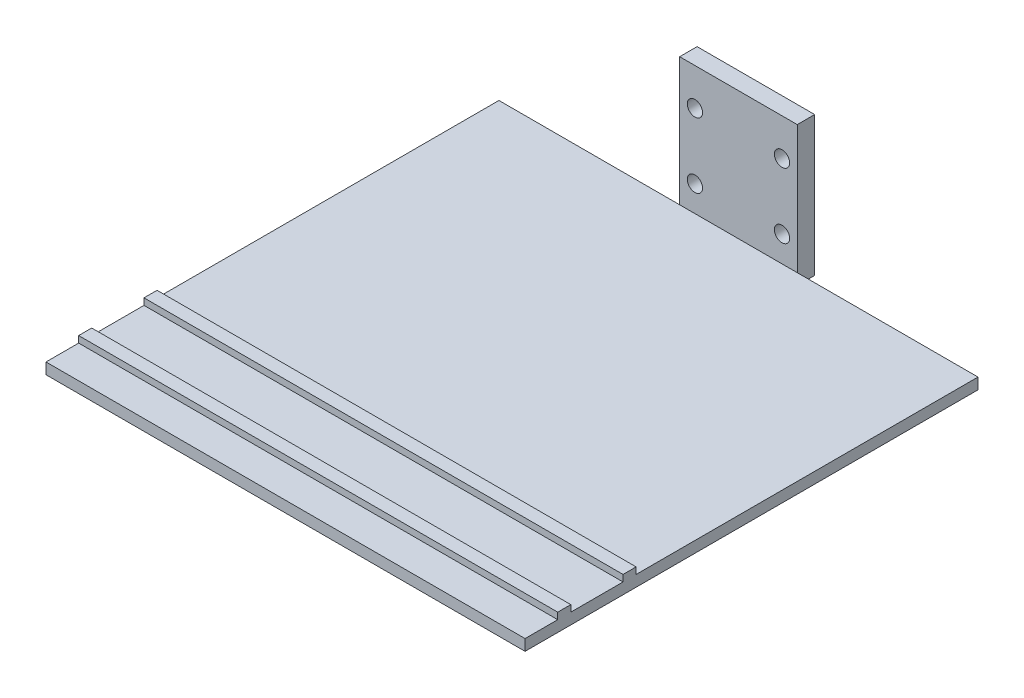
SolidWorks part; units mm, degrees
ref_plane "Piano frontale" through (0, 0, 0) normal (0, 0, 1) x (1, 0, 0)
ref_plane "Piano superiore" through (0, 0, 0) normal (0, 1, 0) x (1, 0, 0)
ref_plane "Piano destro" through (0, 0, 0) normal (1, 0, 0) x (0, 0, -1)
sketch "Schizzo1" plane through (0, 0, 0) normal (0, 0, 1) x (1, 0, 0)
  line L1 (0, 0) -> (27, 0)
  line L2 (0, 0) -> (0, -36)
  line L3 (0, -36) -> (27, -36)
  line L4 (27, 0) -> (27, -36)
  dimension "D1" = 27
  dimension "D2" = 36
extrude "Estrusione-Estrusione1" add sketch "Schizzo1" along normal blind 4
sketch "Schizzo10" plane through (0, 0, 4) normal (0, 0, 1) x (1, 0, 0)
  line L0 (27, 0) -> (0, 0) construction
  line L1 (3.5, -12.5) -> (23.5, -12.5) construction
  line L2 (3.5, -12.5) -> (3.5, -27.5) construction
  line L3 (3.5, -27.5) -> (23.5, -27.5) construction
  line L4 (23.5, -12.5) -> (23.5, -27.5) construction
  line L5 (27, -36) -> (27, 0) construction
  circle A0 centre (3.5, -12.5) radius 1.75
  circle A1 centre (23.5, -12.5) radius 1.75
  circle A2 centre (23.5, -27.5) radius 1.75
  circle A3 centre (3.5, -27.5) radius 1.75
  dimension "D5" = 3.5
  dimension "D1" = 12.5
  dimension "D2" = 15
  dimension "D3" = 20
  dimension "D4" = 3.5
extrude "Taglio-Estrusione5" cut sketch "Schizzo10" against normal blind 10
ref_plane "Piano1" through (13.5, 0, 0) normal (1, 0, 0) x (0, 0, -1)
sketch "Schizzo12" plane through (13.5, 0, 0) normal (1, 0, 0) x (0, 0, -1)
  line L1 (-4, -36) -> (-108, -36)
  line L2 (-4, -36) -> (-4, -33.4507)
  line L3 (-4, -33.4507) -> (-108, -33.4507)
  line L4 (-108, -36) -> (-108, -33.4507)
  dimension "D1" = 104
extrude "Estrusione-Estrusione2" add sketch "Schizzo12" along normal blind 55 and the other way blind 55
sketch "Schizzo14" plane through (-41.5, 0, 0) normal (-1, 0, 0) x (0, 0, 1)
  line L0 (4, -33.4507) -> (108, -33.4507) construction
  line L1 (82.5, -33.4507) -> (85.5, -33.4507)
  line L2 (82.5, -33.4507) -> (82.5, -31.9507)
  line L3 (82.5, -31.9507) -> (85.5, -31.9507)
  line L4 (85.5, -33.4507) -> (85.5, -31.9507)
  line L5 (108, -33.4507) -> (108, -36) construction
  line L6 (97.5, -33.4507) -> (100.5, -33.4507)
  line L7 (97.5, -33.4507) -> (97.5, -31.9507)
  line L8 (97.5, -31.9507) -> (100.5, -31.9507)
  line L9 (100.5, -33.4507) -> (100.5, -31.9507)
  dimension "D1" = 7.5
  dimension "D2" = 12
  dimension "D3" = 1.5
  dimension "D4" = 3
extrude "Estrusione-Estrusione3" add sketch "Schizzo14" against normal blind 110
sketch "Schizzo15" plane through (0, 0, 4) normal (0, 0, 1) x (1, 0, 0)
  line L0 (27, -33.4507) -> (27, 0) construction
  line L1 (0, 0) -> (27, 0)
  line L2 (0, 0) -> (0, -4)
  line L3 (0, -4) -> (27, -4)
  line L4 (27, 0) -> (27, -4)
  dimension "D1" = 4
extrude "Taglio-Estrusione6" cut sketch "Schizzo15" against normal through all
